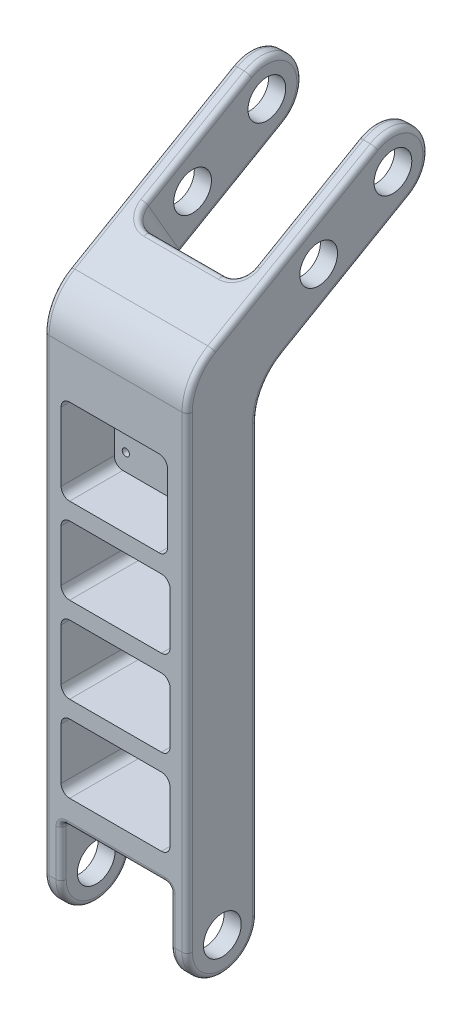
SolidWorks part; units mm, degrees
ref_plane "前视基准面" through (0, 0, 0) normal (0, 0, 1) x (1, 0, 0)
ref_plane "上视基准面" through (0, 0, 0) normal (0, 1, 0) x (1, 0, 0)
ref_plane "右视基准面" through (0, 0, 0) normal (1, 0, 0) x (0, 0, -1)
sketch "草图1" plane through (0, 0, 0) normal (0, 0, 1) x (1, 0, 0)
  line L0 (0, 0) -> (0, 40)
  line L1 (0, 40) -> (83.5, 40)
  line L2 (83.5, 40) -> (83.5, 0)
  line L3 (83.5, 0) -> (73.5, 0)
  line L4 (73.5, 0) -> (73.5, 30)
  line L5 (73.5, 30) -> (10, 30)
  line L6 (10, 30) -> (10, 0)
  line L7 (10, 0) -> (0, 0)
  dimension "D1" = 63.5
  dimension "D2" = 10
  dimension "D3" = 30
  dimension "D4" = 10
extrude "凸台-拉伸1" add sketch "草图1" along normal blind 41
sketch "草图2" plane through (83.5, 0, 0) normal (1, 0, 0) x (0, 0, -1)
  line L0 (-41, 0) -> (0, 0)
  arc A0 (-41, 0) -> (0, 0) centre (-20.5, 0) ccw
extrude "凸台-拉伸2" add sketch "草图2" against normal blind 10
sketch "草图3" plane through (83.5, 0, 0) normal (1, 0, 0) x (0, 0, -1)
  circle A0 centre (-20.5, 0) radius 11
  dimension "D1" = 22
extrude "切除-拉伸1" cut sketch "草图3" against normal blind 10
ref_plane "基准面4" through (41.75, 0, 0) normal (1, 0, 0) x (0, 0, -1)
mirror "镜向1" about plane through (41.75, 0, 0) normal (1, 0, 0) of "凸台-拉伸2", "切除-拉伸1"
sketch "草图4" plane through (0, 40, 0) normal (0, 1, 0) x (1, 0, 0)
  line L0 (83.5, 0) -> (0, 0) construction
  line L1 (0, 0) -> (83.5, 0)
  line L2 (0, 0) -> (0, -41)
  line L3 (0, -41) -> (83.5, -41)
  line L4 (83.5, 0) -> (83.5, -41)
  line L5 (83.5, -41) -> (0, -41) construction
  line L6 (41.75, -41) -> (41.75, 5.4834) construction
extrude "凸台-拉伸3" add sketch "草图4" along normal blind 250
sketch "草图5" plane through (0, 0, 41) normal (0, 0, 1) x (1, 0, 0)
  line L0 (83.5, 0) -> (83.5, 290) construction
  line L1 (15, 45) -> (68.5, 45)
  line L2 (10, 50) -> (10, 80)
  line L3 (15, 85) -> (68.5, 85)
  line L4 (73.5, 50) -> (73.5, 80)
  line L5 (0, 290) -> (0, 0) construction
  line L6 (10, 30) -> (73.5, 30) construction
  line L23 (10, 100) -> (10, 130)
  line L24 (15, 95) -> (68.5, 95)
  line L25 (73.5, 100) -> (73.5, 130)
  line L26 (15, 135) -> (68.5, 135)
  line L27 (10, 150) -> (10, 180)
  line L28 (15, 145) -> (68.5, 145)
  line L29 (73.5, 150) -> (73.5, 180)
  line L30 (15, 185) -> (68.5, 185)
  arc A0 (68.5, 45) -> (73.5, 50) centre (68.5, 50) ccw
  arc A1 (68.5, 85) -> (73.5, 80) centre (68.5, 80) cw
  arc A2 (15, 45) -> (10, 50) centre (15, 50) cw
  arc A3 (10, 80) -> (15, 85) centre (15, 80) cw
  arc A20 (10, 130) -> (15, 135) centre (15, 130) cw
  arc A21 (15, 95) -> (10, 100) centre (15, 100) cw
  arc A22 (68.5, 95) -> (73.5, 100) centre (68.5, 100) ccw
  arc A23 (68.5, 135) -> (73.5, 130) centre (68.5, 130) cw
  arc A24 (10, 180) -> (15, 185) centre (15, 180) cw
  arc A25 (15, 145) -> (10, 150) centre (15, 150) cw
  arc A26 (68.5, 145) -> (73.5, 150) centre (68.5, 150) ccw
  arc A27 (68.5, 185) -> (73.5, 180) centre (68.5, 180) cw
  point P10 (73.5, 45)
  point P13 (73.5, 85)
  dimension "D4" = 5
  dimension "D1" = 10
  dimension "D2" = 10
  dimension "D3" = 40
  dimension "D5" = 15
  dimension "D6" = 3
extrude "切除-拉伸2" cut sketch "草图5" against normal blind 309
sketch "草图7" plane through (83.5, 0, 0) normal (1, 0, 0) x (0, 0, -1)
  line L0 (0, 266.3286) -> (89.1907, 317.8229)
  line L1 (89.1907, 317.8229) -> (68.6907, 353.33)
  line L2 (68.6907, 353.33) -> (-41, 290)
  line L3 (-41, 290) -> (0, 266.3286)
  line L4 (0, 0) -> (0, 290) construction
  circle A1 centre (-20.5, 0) radius 11 construction
  point P3 (78.9407, 335.5764)
  dimension "D1" = 350
  dimension "D2" = 120
  dimension "D3" = 41
extrude "凸台-拉伸5" add sketch "草图7" against normal up to surface (83.5 mm away) up to face at (0, 11, 20.5)
sketch "草图8" plane through (41.75, 0, 0) normal (1, 0, 0) x (0, 0, -1)
  line L0 (0, 236.3286) -> (0, 196.3286)
  line L1 (55, 196.3286) -> (55, 214.3286)
  line L2 (0, 196.3286) -> (55, 196.3286)
  line L5 (55, 214.3286) -> (0, 236.3286)
  line L7 (0, 0) -> (0, 266.3286) construction
  dimension "D1" = 70
  dimension "D2" = 55
  dimension "D3" = 40
  dimension "D4" = 18
extrude "凸台-拉伸6" add sketch "草图8" along normal mid plane 83.5
fillet "圆角1" radius 8 1 edges at (41.75, 196.3286, -55)
sketch "草图10" plane through (83.5, 0, 0) normal (1, 0, 0) x (0, 0, -1)
  circle A0 centre (47, 204.3286) radius 5.5
  dimension "D1" = 11
extrude "切除-拉伸3" cut sketch "草图10" against normal blind 92
sketch "草图11" [suppressed] plane through (52.25, 0, 0) normal (1, 0, 0) x (0, 0, -1)
  line L0 (55, 283.0172) -> (15, 241.915)
  line L1 (55, 242.0172) -> (55, 298.0172) construction
  line L2 (15, 241.915) -> (15, 227.0172)
  line L3 (0, 227.0172) -> (40, 227.0172) construction
  line L4 (15, 227.0172) -> (64.4389, 227.0172)
  line L5 (64.4389, 227.0172) -> (55, 283.0172)
  line L6 (0, 0) -> (0, 243.0172) construction
  dimension "D1" = 15
  dimension "D2" = 15
fillet "圆角2" [suppressed] radius 5
sketch "草图13" plane through (41.75, 0, 0) normal (1, 0, 0) x (0, 0, -1)
  circle A0 centre (47, 204.3286) radius 6
  circle A1 centre (47, 204.3286) radius 5
  dimension "D1" = 10
extrude "凸台-拉伸8" [suppressed] add sketch "草图13" along normal mid plane 1
sketch "草图14" plane through (41.75, 0, 0) normal (1, 0, 0) x (0, 0, -1)
  line L0 (68.6907, 353.33) -> (89.1907, 317.8229)
  arc A0 (68.6907, 353.33) -> (89.1907, 317.8229) centre (78.9407, 335.5764) cw
extrude "凸台-拉伸9" add sketch "草图14" against normal mid plane 83.5
sketch "草图15" plane through (83.5, 0, 0) normal (1, 0, 0) x (0, 0, -1)
  line L0 (0, 266.3286) -> (89.1907, 317.8229) construction
  circle A0 centre (78.9407, 335.5764) radius 11
  circle A1 centre (35.6394, 310.5764) radius 11
  dimension "D1" = 22
  dimension "D2" = 22
  dimension "D3" = 50
  dimension "D4" = 20.5
extrude "切除-拉伸5" cut sketch "草图15" against normal mid plane 185
sketch "草图16" plane through (0, 235.2535, 135.8237) normal (0, 0.866, 0.5) x (1, 0, 0)
  line L0 (83.5, 256.6529) -> (0, 256.6529) construction
  line L1 (10, 256.6529) -> (73.5, 256.6529)
  line L2 (10, 256.6529) -> (10, 156.6529)
  line L3 (10, 156.6529) -> (73.5, 156.6529)
  line L4 (73.5, 256.6529) -> (73.5, 156.6529)
  line L5 (83.5, 236.1529) -> (83.5, 109.493) construction
  line L6 (0, 109.493) -> (0, 236.1529) construction
  dimension "D1" = 10
  dimension "D2" = 10
  dimension "D3" = 100
extrude "切除-拉伸6" cut sketch "草图16" against normal blind 65
sketch "草图17" plane through (10, 0, 0) normal (1, 0, 0) x (0, 0, -1)
  circle A0 centre (35.6394, 310.5764) radius 9.5
  circle A1 centre (35.6394, 310.5764) radius 7.5
  dimension "D1" = 15
extrude "凸台-拉伸10" [suppressed] add sketch "草图17" against normal blind 4
sketch "草图18" [suppressed] plane through (73.5, 0, 0) normal (-1, 0, 0) x (0, 0, 1)
  circle A0 centre (-35.6394, 310.5764) radius 7.5
  circle A1 centre (-35.6394, 310.5764) radius 9.5
extrude "凸台-拉伸11" [suppressed] add sketch "草图18" against normal blind 4
fillet "圆角3" radius 30 2 edges at (41.75, 290, 41) (41.75, 266.3286, 0)
extrude "切除-拉伸7" cut sketch "草图8<2>" against normal mid plane 75.5
sketch "草图8<2>" plane through (41.75, 0, 0) normal (1, 0, 0) x (0, 0, -1) same geometry as "草图8"
fillet "圆角4" [suppressed] radius 8
sketch "草图19" plane through (83.5, 0, 0) normal (1, 0, 0) x (0, 0, -1)
  line L1 (0, 236.3286) -> (70.1752, 236.3286)
  line L2 (0, 236.3286) -> (0, 190.676)
  line L3 (0, 190.676) -> (70.1752, 190.676)
  line L4 (70.1752, 236.3286) -> (70.1752, 190.676)
extrude "切除-拉伸8" cut sketch "草图19" against normal blind 90.5
sketch "草图20" plane through (0, 0, 0) normal (0, 0, -1) x (-1, 0, 0)
  line L1 (-66.75, 225) -> (-16.75, 225) construction
  line L2 (-66.75, 225) -> (-66.75, 205) construction
  line L3 (-66.75, 205) -> (-16.75, 205) construction
  line L4 (-16.75, 225) -> (-16.75, 205) construction
  line L5 (-66.75, 225) -> (-16.75, 205) construction
  line L6 (-66.75, 205) -> (-16.75, 225) construction
  point P0 (-41.75, 215)
  dimension "D1" = 41.75
  dimension "D2" = 215
  dimension "D3" = 20
  dimension "D4" = 50
hole_wizard "M5 螺纹孔的螺纹孔钻头1" positions "3D草图1" profile "草图21" hole size "M5" standard "GB"
sketch3d "3D草图1"
  point P0 (66.75, 225, 0)
  point P3 (16.75, 225, 0)
  point P6 (16.75, 205, 0)
  point P9 (66.75, 205, 0)
sketch "草图21" plane through (66.75, 225, 0) normal (1, 0, 0) x (0, 1, 0)
  line L0 (0, 0) -> (0, 11.2618)
  line L1 (0, 11.2618) -> (2.1, 10)
  line L2 (2.1, 10) -> (2.1, 0)
  line L5 (2.1, 0) -> (0, 0)
  line L10 (0, 11.2618) -> (-2.1, 10) construction
  line L11 (0, -6.35) -> (0, 107.95) construction
  dimension "孔直径" = 4.2
  dimension "孔深度" = 10
  dimension "导头角度" = 118
fillet "圆角5" radius 10 2 edges at (10, 295.8264, -10.0917) (73.5, 295.8264, -10.0917)
sketch "草图22" plane through (0, 0, 41) normal (0, 0, 1) x (1, 0, 0)
  line L0 (68.5, 185) -> (15, 185) construction
  line L1 (15, 195) -> (67.0355, 195)
  line L2 (10, 200) -> (10, 240)
  line L3 (15, 245) -> (67.0355, 245)
  line L4 (72.0355, 200) -> (72.0355, 240)
  arc A0 (10, 240) -> (15, 245) centre (15, 240) cw
  arc A1 (67.0355, 245) -> (72.0355, 240) centre (67.0355, 240) cw
  arc A2 (67.0355, 195) -> (72.0355, 200) centre (67.0355, 200) ccw
  arc A3 (15, 195) -> (10, 200) centre (15, 200) cw
  point P10 (72.0355, 245)
  point P13 (72.0355, 195)
  dimension "D3" = 5
  dimension "D1" = 10
  dimension "D2" = 50
extrude "切除-拉伸9" cut sketch "草图22" against normal blind 31
fillet "圆角6" radius 3 38 edges at (10, -20.5, 20.5) (73.5, -20.5, 20.5) (10, 15, 41) (10, 15, 0) (73.5, 15, 41) (73.5, 15, 0) (70.5711, 279.5374, -22.8782) (73.5, 300.4479, -59.0963) (73.5, 345.8264, -96.6942) (73.5, 335.955, -38.5963) (70.5711, 315.0444, -2.3782) (12.9289, 315.0444, -2.3782) (10, 335.955, -38.5963) (10, 345.8264, -96.6942) (10, 300.4479, -59.0963) (12.9289, 279.5374, -22.8782) (0, 287.6795, 36.9808) (0, 325.9951, -21.3454) (0, 345.8264, -96.6942) (0, 296.4059, -52.0954) (0, 264.0081, -4.0192) (0, 124.5041, 0) (0, -20.5, 20.5) (83.5, -20.5, 20.5) (83.5, 136.3397, 41) (83.5, 287.6795, 36.9808) (83.5, 325.9951, -21.3454) (83.5, 345.8264, -96.6942) (83.5, 296.4059, -52.0954) (83.5, 264.0081, -4.0192) (10, 30, 20.5) (41.75, 30, 41) (73.5, 30, 20.5) (41.75, 30, 0) (41.75, 313.58, 0.1583) (41.75, 278.0729, -20.3417) (0, 136.3397, 41) (83.5, 124.5041, 0)
